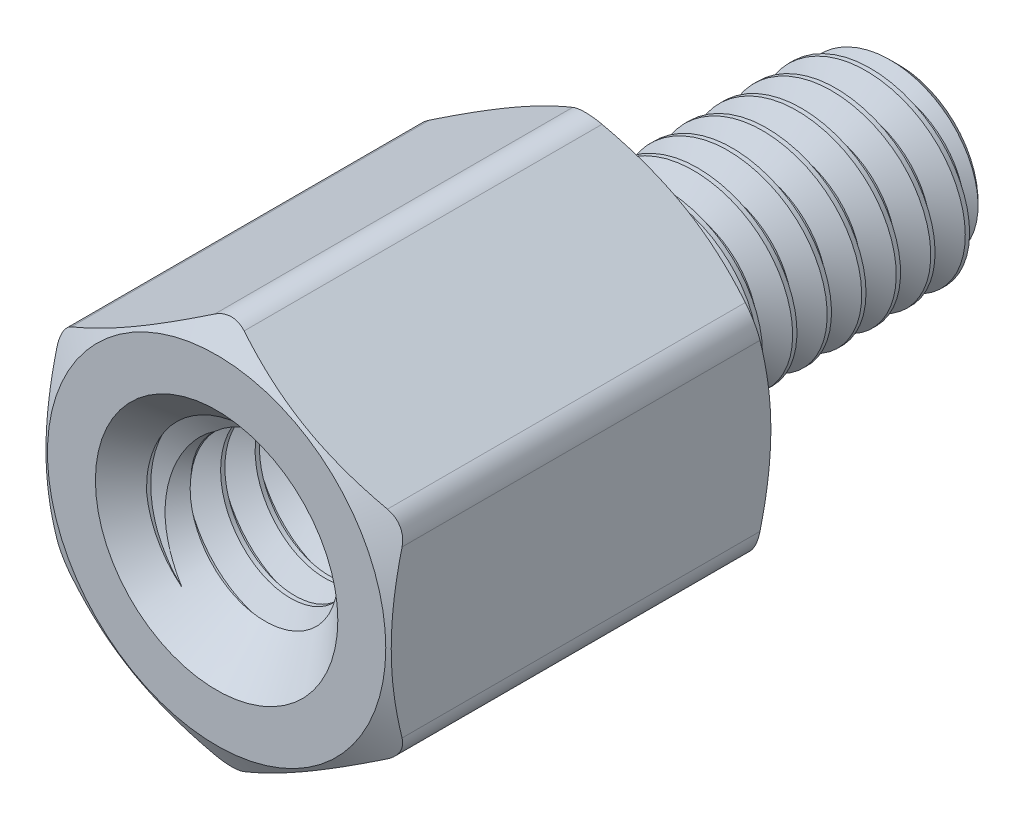
SolidWorks part; units mm, degrees
ref_plane "Front Plane" through (0, 0, 0) normal (0, 0, 1) x (1, 0, 0)
ref_plane "Top Plane" through (0, 0, 0) normal (0, 1, 0) x (1, 0, 0)
ref_plane "Right Plane" through (0, 0, 0) normal (1, 0, 0) x (0, 0, -1)
sketch "Sketch1" plane through (0, 0, 0) normal (0, 0, 1) x (1, 0, 0)
  line L1 (2.25, 1.299) -> (0, 2.5981)
  line L2 (0, 2.5981) -> (-2.25, 1.299)
  line L3 (-2.25, 1.299) -> (-2.25, -1.299)
  line L4 (-2.25, -1.299) -> (0, -2.5981)
  line L5 (0, -2.5981) -> (2.25, -1.299)
  line L6 (2.25, -1.299) -> (2.25, 1.299)
  circle A0 centre (0, 0) radius 2.25 construction
  point P10 (0, -2.25)
  dimension "Hex Size" = 4.5
sketch "Sketch2" plane through (0, 0, 0) normal (1, 0, 0) x (0, 0, -1)
  line L0 (3.9, 0) -> (-5, 0) construction
  line L2 (0, 1.25) -> (0, -1.25) construction
  line L3 (-3.1, 1.25) -> (-3.1, -1.25) construction
  line L4 (-5.4219, 1.2987) -> (-5.1969, 0.909) construction
  line L5 (-5.1969, 0.909) -> (-4.9719, 1.2987) construction
  line L6 (-4.9719, 1.2987) -> (-5.4219, 1.2987) construction
  line L7 (-5.3938, 1.25) -> (-5, 1.25) construction
  line L8 (-5.225, 0.9577) -> (-5.1688, 0.9577) construction
  line L9 (-5.1969, 0.9577) -> (-5.1969, 0.909) construction
  line L10 (-5.1969, 1.25) -> (-5.1969, 1.2987) construction
  line L11 (3.8719, 1.2987) -> (4.3219, 1.2987) construction
  line L12 (4.3219, 1.2987) -> (4.0969, 0.909) construction
  line L13 (4.0969, 0.909) -> (3.8719, 1.2987) construction
  line L14 (3.9, 1.25) -> (4.2937, 1.25) construction
  line L15 (4.0687, 0.9577) -> (4.125, 0.9577) construction
  line L16 (4.0969, 0.9577) -> (4.0969, 0.909) construction
  line L17 (4.0969, 1.25) -> (4.0969, 1.2987) construction
  line L18 (0, 2.5981) -> (-5, 2.5981) construction
  point P6 (0, 0)
  point P9 (-3.1, 0)
  dimension "Length" = 5
sketch "Sketch3" plane through (0, 0, 0) normal (1, 0, 0) x (0, 0, -1)
  line L0 (-3.1, 0) -> (3.9, 0)
  line L1 (-3.1, 1.25) -> (-3.1, -1.25) construction
  line L2 (3.9, 0) -> (3.9, 1.025)
  line L3 (3.9, 1.025) -> (3.675, 1.25)
  line L4 (3.675, 1.25) -> (0.6367, 1.25)
  line L5 (0.6367, 1.25) -> (0.468, 0.9577)
  line L6 (-3.1, 0) -> (-3.1, 1.025)
  line L7 (-3.1, 1.025) -> (-3.325, 1.25)
  line L8 (-3.325, 1.25) -> (-4.775, 1.25)
  line L9 (-4.775, 1.25) -> (-5, 1.475)
  line L10 (3.675, 0) -> (3.675, -1.25) construction
  line L11 (-5, 1.475) -> (-5, 2.25)
  line L12 (-5, 2.25) -> (0, 2.25)
  line L14 (0.468, 0.9577) -> (0.225, 0.9577)
  line L15 (0, 1.1827) -> (0, 2.25)
  arc A0 (0, 1.1827) -> (0.225, 0.9577) centre (0.225, 1.1827) ccw
  point P5 (-5, -2.25)
  point P8 (-3.875, -1.25)
  point P9 (2.775, -1.25)
  point P27 (0, 0.9577)
  dimension "D4" = 0.225
  dimension "D2" = 0.225
  dimension "D1" = 45
  dimension "D6" = 1.125
  dimension "D7" = 60
  dimension "D3" = 1.125
  dimension "D5" = 0.468
revolve "Revolve1" add sketch "Sketch3" angle 360 about L0 region at (0, 1.0326, 0.6702)
sketch "Sketch4" plane through (0, 0, 5) normal (0, 0, 1) x (1, 0, 0)
  line L0 (0, 2.25) -> (0, 1.25) construction
  line L1 (-2.25, 1.299) -> (-2.25, -1.299)
  line L2 (-2.25, -1.299) -> (0, -2.5981)
  line L3 (0, -2.5981) -> (2.25, -1.299)
  line L4 (2.25, -1.299) -> (2.25, 1.299)
  line L5 (2.25, 1.299) -> (0, 2.5981)
  line L6 (0, 2.5981) -> (-2.25, 1.299)
  circle A0 centre (0, 0) radius 2.25 construction
  circle A1 centre (0, 0) radius 1.75
  circle A2 centre (0, 0) radius 2.25 construction
  point P16 (0, 1.75)
extrude "Boss-Extrude1" add sketch "Sketch4" against normal up to surface (5 mm away) up to face at (0, 2.25, 0)
sketch "Sketch5" plane through (0, 0, 5) normal (0, 0, 1) x (1, 0, 0)
  line L0 (-0.717, 1.0239) -> (0.717, -1.0239) construction
  line L1 (0, 1.25) -> (0, -1.25) construction
  line L3 (0, -2.7928) -> (0, 2.7928) construction
  circle A0 centre (0, 0) radius 2.205
  point P11 (0.717, -1.0239)
  dimension "D1" = 4.41
  dimension "D2" = 35
extrude "Cut-Extrude1" cut sketch "Sketch5" against normal through all draft 60 flip side to cut
sketch "Sketch6" plane through (0, 0, 0) normal (0, 0, -1) x (-1, 0, 0)
  circle A0 centre (0, 0) radius 2.205
  circle A1 centre (0, 0) radius 2.205 construction
extrude "Cut-Extrude2" cut sketch "Sketch6" against normal through all draft 60 flip side to cut
fillet "Fillet1" radius 0.3825 6 edges at (0, 2.5981, 2.5) (-2.25, -1.299, 2.5) (0, -2.5981, 2.5) (2.25, -1.299, 2.5) (2.25, 1.299, 2.5) (-2.25, 1.299, 2.5)
sketch "Drawing1" plane through (0, 0, 0) normal (1, 0, 0) x (0, 0, -1)
  line L0 (-5, 1.25) -> (-3.1, 1.25) construction
  line L1 (-3.1, 1.25) -> (-3.1, -1.25) construction
  line L2 (-3.1, -1.25) -> (-5, -1.25) construction
sketch "Sketch7" plane through (0, 0, 0) normal (-1, 0, 0) x (0, 0, 1)
  line L0 (-4.0687, 0.9577) -> (-4.125, 0.9577)
  line L1 (-4.125, 0.9577) -> (-4.3078, 1.2744)
  line L2 (-4.3219, 1.2987) -> (-4.0969, 0.909) construction
  line L3 (-4.3078, 1.2744) -> (-3.8859, 1.2744)
  line L4 (-4.0969, 0.909) -> (-3.8719, 1.2987) construction
  line L5 (-3.8859, 1.2744) -> (-4.0687, 0.9577)
  line L6 (-4.0969, 1.25) -> (-4.0969, 1.2987) construction
  point P12 (-4.0969, 1.2744)
sketch "Sketch8" plane through (0, 0, -3.9) normal (0, 0, -1) x (-1, 0, 0)
  circle A0 centre (0, 0) radius 1.25
curve "Helix/Spiral1" pitch 0.45 height 3.783 radius 1.25 centre (0, 0, -3.9) axis (0, 0, 1) start towards (0, 1, 0)
sweep "Cut-Sweep1" cut profiles "Sketch7" path "Helix/Spiral1" align with end faces yes
sketch "Sketch9" plane through (0, 0, 3.1) normal (0, 0, 1) x (1, 0, 0)
  circle A0 centre (0, 0) radius 1.475
extrude "Boss-Extrude2" add sketch "Sketch9" along normal up to surface (1.9 mm away) up to face at (0, 1.475, 5)
sketch "Sketch10" plane through (0, 0, 0) normal (1, 0, 0) x (0, 0, -1)
  line L0 (3.9, 0) -> (-5, 0) construction
  line L1 (-3.1, 1.25) -> (-5, 1.25)
  line L2 (-3.1, 1.25) -> (-3.1, 0)
  line L3 (-3.1, 0) -> (-5, 0)
  line L4 (-5, 1.25) -> (-5, 0)
revolve "Revolve2" add sketch "Sketch10" angle 360 about L0
sketch "Sketch11" plane through (0, 0, 5) normal (0, 0, 1) x (1, 0, 0)
  circle A0 centre (0, 0) radius 1.25
  circle A1 centre (0, 0) radius 1.25 construction
sketch "Sketch12" plane through (0, 0, 0) normal (1, 0, 0) x (0, 0, -1)
  line L0 (-5.225, 0.9577) -> (-5.1688, 0.9577)
  line L1 (-5.1688, 0.9577) -> (-4.9859, 1.2744)
  line L2 (-5.1969, 0.909) -> (-4.9719, 1.2987) construction
  line L3 (-4.9859, 1.2744) -> (-5.4078, 1.2744)
  line L4 (-5.4219, 1.2987) -> (-5.1969, 0.909) construction
  line L5 (-5.4078, 1.2744) -> (-5.225, 0.9577)
  line L6 (-5.1969, 1.25) -> (-5.1969, 1.2987) construction
  point P12 (-5.1969, 1.2744)
curve "Helix/Spiral2" pitch 0.45 height 2.35 radius 1.25 centre (0, 0, 5) axis (0, 0, -1) start towards (0, 1, 0)
sweep "Cut-Sweep2" cut profiles "Sketch12" path "Helix/Spiral2" align with end faces yes
combine bodies "Combine1" operation type subtract main body 113 bodies to subtract 114
sketch "Sketch13" plane through (0, 0, 5) normal (0, 0, 1) x (1, 0, 0)
  circle A0 centre (0, 0) radius 1.58
  dimension "D1" = 3.16
extrude "Cut-Extrude3" cut sketch "Sketch13" against normal through all draft 45
equation "\"Thread Pitch (B)/8@Sketch2\" = \"Thread Pitch (B)@Sketch2\" / 8"
equation "\"Thread Pitch (A)/8@Sketch2\" = \"Thread Pitch (A)@Sketch2\" / 8"
equation "\"D1@Sketch5\"=\"Hex Size@Sketch1\" * .98"
equation "\"D1@Fillet1\"=\"Hex Size@Sketch1\" * .085"
equation "\"D2@Sketch3\"=\"Thread Pitch (A)@Sketch2\" * .5"
equation "\"D4@Sketch3\" = \"D2@Sketch3\""
equation "\"D6@Sketch3\" = \"Thread Pitch (A)@Sketch2\" * 2.5"
equation "\"D3@Helix/Spiral1\" = \"Thread Length (A)@Sketch2\" - \"D5@Sketch3\" * .25"
equation "\"D4@Helix/Spiral1\" = \"Thread Pitch (A)@Sketch2\""
equation "\"D3@Sketch3\" = \"Thread Pitch (B)@Sketch2\" * 2.5"
equation "\"D5@Sketch3\" = \"Thread Length (A)@Sketch2\" * .12"
equation "\"D3@Helix/Spiral2\" = \"Minimum Thread Length (B)@Sketch2\" + \"Thread Pitch (B)@Sketch2\""
equation "\"D4@Helix/Spiral2\" = \"Thread Pitch (B)@Sketch2\""
equation "\"D1@Sketch13\"=(\"Hex Size@Sketch1\"-\"Thread Size (A)@Sketch2\")*.33+\"Thread Size (A)@Sketch2\""
